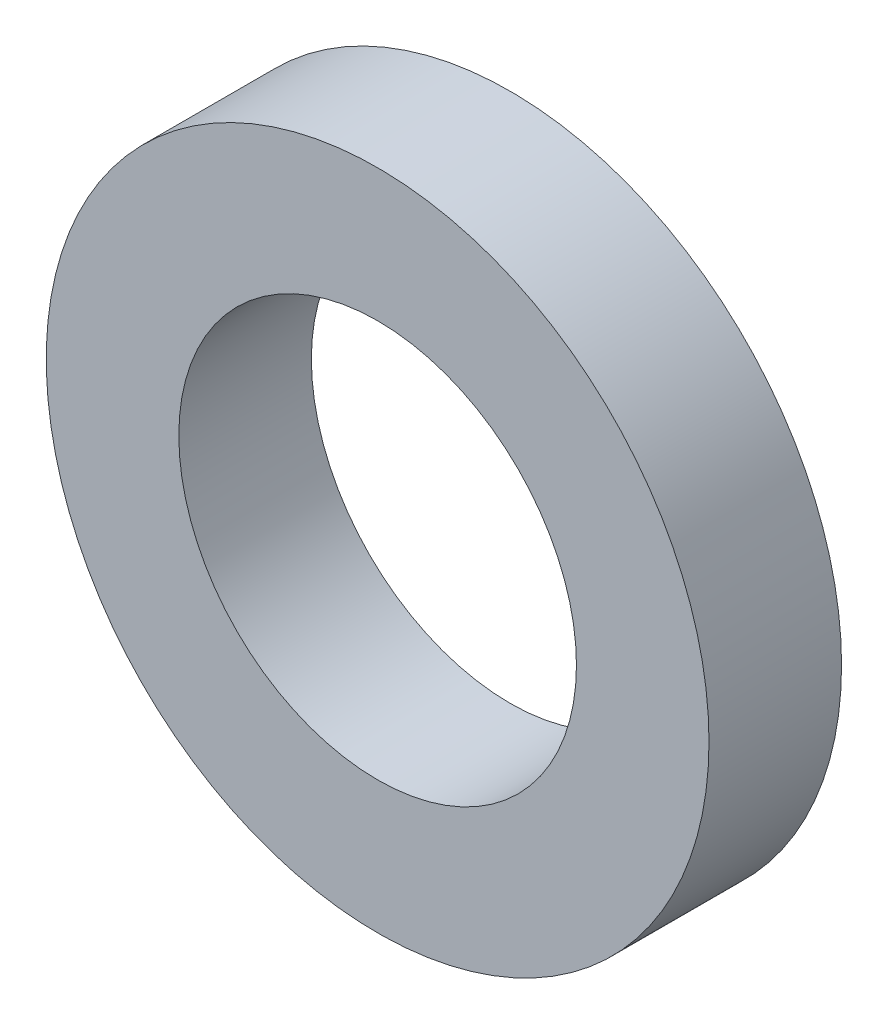
SolidWorks part; units mm, degrees
ref_plane "Front" through (0, 0, 0) normal (0, 0, 1) x (1, 0, 0)
ref_plane "Top" through (0, 0, 0) normal (0, 1, 0) x (1, 0, 0)
ref_plane "Right" through (0, 0, 0) normal (1, 0, 0) x (0, 0, -1)
sketch "Sketch1" plane through (0, 0, 0) normal (0, 0, 1) x (1, 0, 0)
  circle A0 centre (0, 0) radius 31.75
  circle A1 centre (0, 0) radius 19.05
  dimension "D1" = 38.1
  dimension "D2" = 63.5
extrude "Boss-Extrude1" add sketch "Sketch1" along normal blind 12.7
